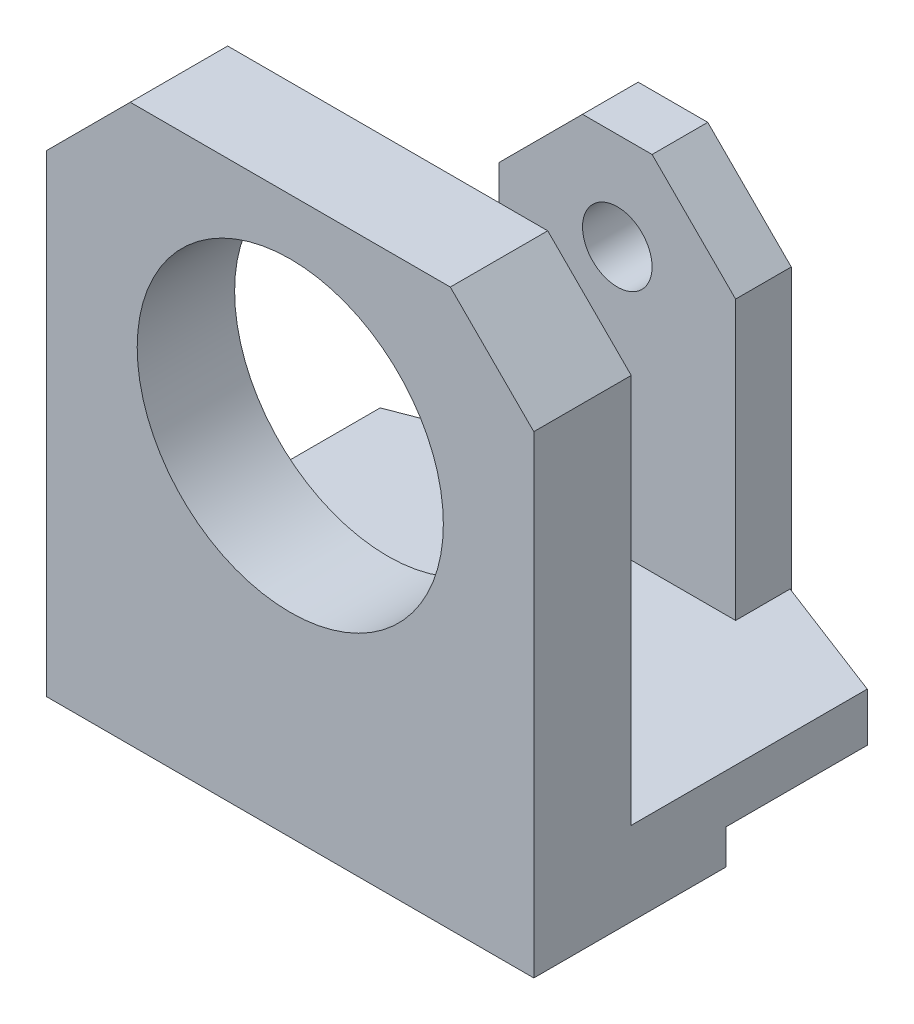
SolidWorks part; units mm, degrees
ref_plane "Front Plane" through (0, 0, 0) normal (0, 0, 1) x (1, 0, 0)
ref_plane "Top Plane" through (0, 0, 0) normal (0, 1, 0) x (1, 0, 0)
ref_plane "Right Plane" through (0, 0, 0) normal (1, 0, 0) x (0, 0, -1)
sketch "Sketch1" plane through (0, 0, 0) normal (0, 0, 1) x (1, 0, 0)
  line L0 (-17.5, 15) -> (-17.5, -25)
  line L1 (-17.5, -25) -> (17.5, -25)
  line L2 (17.5, -25) -> (17.5, 15)
  line L3 (17.5, 15) -> (-17.5, 15)
  circle A0 centre (0, 0) radius 11
  point P5 (0, 15)
  dimension "D1" = 22
  dimension "D2" = 25
  dimension "D3" = 40
  dimension "D4" = 35
extrude "Boss-Extrude1" add sketch "Sketch1" along normal blind 7
sketch "Sketch2" plane through (0, 0, 0) normal (0, 0, -1) x (-1, 0, 0)
  line L0 (-17.5, -19) -> (17.5, -19)
  line L1 (-17.5, -25) -> (-17.5, 15) construction
  line L2 (17.5, 15) -> (17.5, -25) construction
  line L3 (17.5, -19) -> (17.5, -25)
  line L4 (17.5, -25) -> (-17.5, -25)
  line L5 (-17.5, -25) -> (-17.5, -19)
  dimension "D1" = 6
extrude "Boss-Extrude2" add sketch "Sketch2" along normal blind 16.5
sketch "Sketch3" plane through (0, 0, -16.5) normal (0, 0, -1) x (-1, 0, 0)
  line L0 (-8.5, -25) -> (-8.5, 7)
  line L1 (-17.5, -25) -> (17.5, -25) construction
  line L2 (-8.5, 7) -> (8.5, 7)
  line L3 (8.5, 7) -> (8.5, -25)
  line L4 (8.5, -25) -> (-8.5, -25)
  circle A0 centre (0, 0) radius 2.5
  point P4 (0, 7)
  point P7 (0, -25)
  dimension "D3" = 5
  dimension "D1" = 17
  dimension "D2" = 32
extrude "Boss-Extrude3" add sketch "Sketch3" along normal blind 4
chamfer "Chamfer1" distance 10.2 angle 21 2 edges at (-8.5, -22, -16.5) (8.5, -22, -16.5) first distance on face at (-13, -22, -16.5) first distance on face at (13, -22, -16.5)
chamfer "Chamfer2" distance 6 4 edges at (-17.5, 15, 3.5) (-8.5, 7, -18.5) (8.5, 7, -18.5) (17.5, 15, 3.5)
sketch "Sketch4" plane through (0, 0, -20.5) normal (0, 0, -1) x (-1, 0, 0)
  line L0 (17.5, -19) -> (17.5, -25) construction
  line L1 (-17.5, -25) -> (17.5, -25)
  line L2 (-17.5, -25) -> (-17.5, -22.5)
  line L3 (-17.5, -22.5) -> (17.5, -22.5)
  line L4 (17.5, -25) -> (17.5, -22.5)
  dimension "D1" = 2.5
extrude "Cut-Extrude1" cut sketch "Sketch4" against normal blind 13.7
